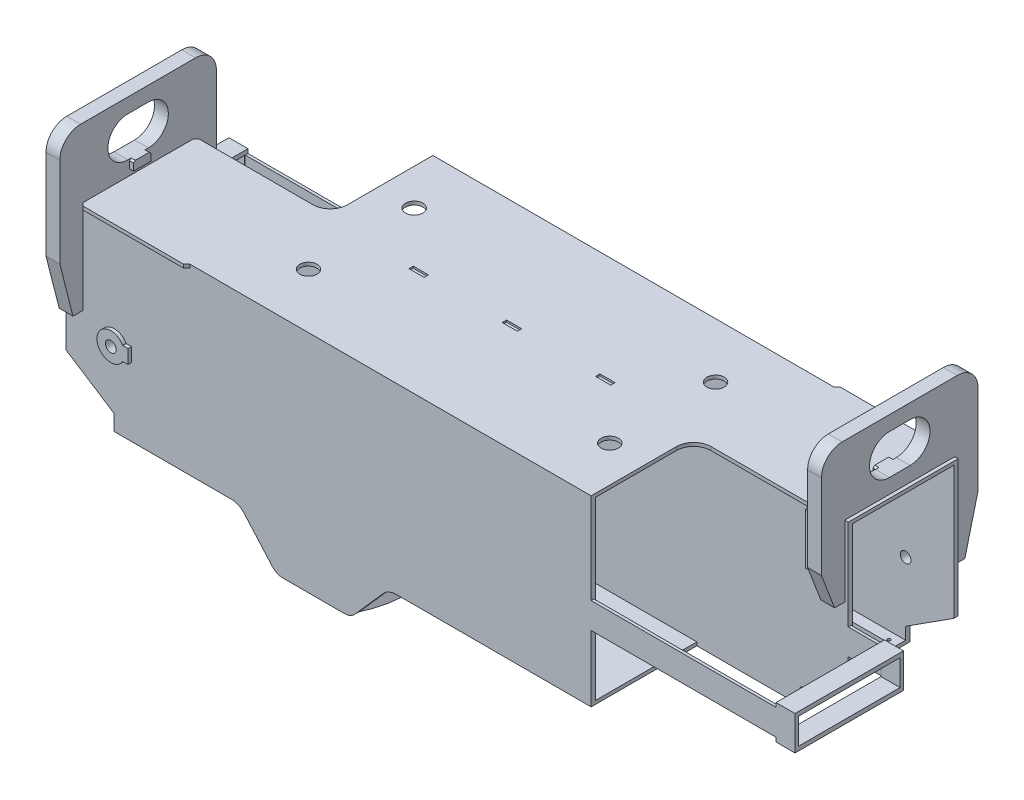
SolidWorks part; units mm, degrees
ref_plane "正面" through (0, 0, 0) normal (0, 0, 1) x (1, 0, 0)
ref_plane "平面" through (0, 0, 0) normal (0, 1, 0) x (1, 0, 0)
ref_plane "右側面" through (0, 0, 0) normal (1, 0, 0) x (0, 0, -1)
ref_plane "平面1" through (0, 0, -306) normal (0, 0, 1) x (1, 0, 0)
sketch "ｽｹｯﾁ2" plane through (0, 0, -306) normal (0, 0, 1) x (1, 0, 0)
  line L0 (140, 0) -> (478.29, 0)
  line L1 (515.7605, -16.8947) -> (597.5636, -109.4842)
  line L2 (627.54, -123) -> (806.46, -123)
  line L3 (836.4364, -109.4842) -> (918.2395, -16.8947)
  line L4 (955.71, 0) -> (1002.29, 0)
  line L5 (1039.7605, -16.8947) -> (1121.5636, -109.4842)
  line L6 (1151.54, -123) -> (1330.46, -123)
  line L7 (1360.4364, -109.4842) -> (1442.2395, -16.8947)
  line L8 (1479.71, 0) -> (1818, 0)
  line L9 (1818, 0) -> (1818, 45)
  line L10 (1818, 45) -> (1958, 135)
  line L11 (1958, 135) -> (1958, 519)
  line L12 (1958, 519) -> (0, 519)
  line L13 (0, 519) -> (0, 135)
  line L14 (0, 135) -> (140, 45)
  line L15 (140, 45) -> (140, 0)
  arc A0 (478.29, 0) -> (515.7605, -16.8947) centre (478.29, -50) cw
  arc A1 (597.5636, -109.4842) -> (627.54, -123) centre (627.54, -83) ccw
  arc A2 (806.46, -123) -> (836.4364, -109.4842) centre (806.46, -83) ccw
  arc A3 (918.2395, -16.8947) -> (955.71, 0) centre (955.71, -50) cw
  arc A4 (1002.29, 0) -> (1039.7605, -16.8947) centre (1002.29, -50) cw
  arc A5 (1121.5636, -109.4842) -> (1151.54, -123) centre (1151.54, -83) ccw
  arc A6 (1330.46, -123) -> (1360.4364, -109.4842) centre (1330.46, -83) ccw
  arc A7 (1442.2395, -16.8947) -> (1479.71, 0) centre (1479.71, -50) cw
extrude "ﾎﾞｽ - 押し出し1" add sketch "ｽｹｯﾁ2" against normal blind 12
sketch "ｽｹｯﾁ3" plane through (0, 0, 0) normal (0, 0, 1) x (1, 0, 0)
  line L0 (140, 0) -> (478.29, 0)
  line L1 (515.7605, -16.8947) -> (597.5636, -109.4842)
  line L2 (627.54, -123) -> (806.46, -123)
  line L3 (836.4364, -109.4842) -> (918.2395, -16.8947)
  line L4 (955.71, 0) -> (1520, 0)
  line L5 (1520, 0) -> (1520, 519)
  line L6 (1520, 519) -> (0, 519)
  line L7 (0, 519) -> (0, 135)
  line L8 (0, 135) -> (140, 45)
  line L9 (140, 45) -> (140, 0)
  arc A0 (478.29, 0) -> (515.7605, -16.8947) centre (478.29, -50) cw
  arc A1 (597.5636, -109.4842) -> (627.54, -123) centre (627.54, -83) ccw
  arc A2 (806.46, -123) -> (836.4364, -109.4842) centre (806.46, -83) ccw
  arc A3 (918.2395, -16.8947) -> (955.71, 0) centre (955.71, -50) cw
extrude "ﾎﾞｽ - 押し出し2" add sketch "ｽｹｯﾁ3" against normal blind 12
sketch "ｽｹｯﾁ4" plane through (0, 0, 0) normal (0, 0, 1) x (1, 0, 0)
  circle A0 centre (140, 218) radius 15.5
extrude "ｶｯﾄ - 押し出し1" cut sketch "ｽｹｯﾁ4" against normal blind 12
ref_plane "平面2" through (0, 0, -612) normal (0, 0, 1) x (1, 0, 0)
sketch "ｽｹｯﾁ6" plane through (0, 0, -612) normal (0, 0, 1) x (1, 0, 0)
  line L0 (1818, 0) -> (1479.71, 0)
  line L1 (1442.2395, -16.8947) -> (1360.4364, -109.4842)
  line L2 (1330.46, -123) -> (1151.54, -123)
  line L3 (1121.5636, -109.4842) -> (1039.7605, -16.8947)
  line L4 (1002.29, 0) -> (438, 0)
  line L5 (438, 0) -> (438, 519)
  line L6 (438, 519) -> (1958, 519)
  line L7 (1958, 519) -> (1958, 135)
  line L8 (1958, 135) -> (1818, 45)
  line L9 (1818, 45) -> (1818, 0)
  arc A0 (1479.71, 0) -> (1442.2395, -16.8947) centre (1479.71, -50) ccw
  arc A1 (1360.4364, -109.4842) -> (1330.46, -123) centre (1330.46, -83) cw
  arc A2 (1151.54, -123) -> (1121.5636, -109.4842) centre (1151.54, -83) cw
  arc A3 (1039.7605, -16.8947) -> (1002.29, 0) centre (1002.29, -50) ccw
extrude "ﾎﾞｽ - 押し出し3" add sketch "ｽｹｯﾁ6" against normal blind 12
sketch "ｽｹｯﾁ7" plane through (0, 0, -612) normal (0, 0, 1) x (1, 0, 0)
  circle A0 centre (1818, 218) radius 15.5
extrude "ｶｯﾄ - 押し出し2" cut sketch "ｽｹｯﾁ7" against normal blind 12
ref_plane "平面3" through (0, 519, 0) normal (0, 1, 0) x (1, 0, 0)
sketch "ｽｹｯﾁ9" plane through (0, 519, 0) normal (0, 1, 0) x (1, 0, 0)
  line L0 (0, 0) -> (50, 0)
  line L1 (50, 0) -> (59, -9)
  line L2 (59, -9) -> (350, -9)
  line L3 (350, -9) -> (359, 0)
  line L4 (359, 0) -> (1520, 0)
  line L5 (1520, 0) -> (1520, 247)
  line L6 (1570, 297) -> (1899, 297)
  line L7 (1899, 297) -> (1908, 306)
  line L8 (1908, 306) -> (1958, 306)
  line L9 (1958, 306) -> (1958, 624)
  line L10 (1958, 624) -> (1908, 624)
  line L11 (1908, 624) -> (1899, 633)
  line L12 (1899, 633) -> (1608, 633)
  line L13 (1608, 633) -> (1599, 624)
  line L14 (1599, 624) -> (438, 624)
  line L15 (438, 624) -> (438, 377)
  line L16 (388, 327) -> (59, 327)
  line L17 (59, 327) -> (50, 318)
  line L18 (50, 318) -> (0, 318)
  line L19 (0, 318) -> (0, 0)
  arc A0 (1520, 247) -> (1570, 297) centre (1570, 247) cw
  arc A1 (438, 377) -> (388, 327) centre (388, 377) cw
extrude "ﾎﾞｽ - 押し出し4" add sketch "ｽｹｯﾁ9" along normal blind 10
sketch "ｽｹｯﾁ10" plane through (0, 519, 0) normal (0, 1, 0) x (1, 0, 0)
  circle A0 centre (543, 159) radius 25
  circle A1 centre (1415, 159) radius 25
  circle A2 centre (543, 465) radius 25
  circle A3 centre (1415, 465) radius 25
sketch "ｽｹｯﾁ11" plane through (0, 519, 0) normal (0, 1, 0) x (1, 0, 0)
  circle A0 centre (543, 159) radius 25
  circle A1 centre (1415, 159) radius 25
  circle A2 centre (543, 465) radius 25
  circle A3 centre (1415, 465) radius 25
extrude "ｶｯﾄ - 押し出し4" cut sketch "ｽｹｯﾁ11" along normal blind 10
sketch "ｽｹｯﾁ12" plane through (0, 519, 0) normal (0, 1, 0) x (1, 0, 0)
  line L0 (687, 305.75) -> (731, 305.75)
  line L1 (731, 305.75) -> (731, 318.25)
  line L2 (731, 318.25) -> (687, 318.25)
  line L3 (687, 318.25) -> (687, 305.75)
  line L4 (957, 305.75) -> (1001, 305.75)
  line L5 (1001, 305.75) -> (1001, 318.25)
  line L6 (1001, 318.25) -> (957, 318.25)
  line L7 (957, 318.25) -> (957, 305.75)
  line L8 (1227, 305.75) -> (1271, 305.75)
  line L9 (1271, 305.75) -> (1271, 318.25)
  line L10 (1271, 318.25) -> (1227, 318.25)
  line L11 (1227, 318.25) -> (1227, 305.75)
sketch "ｽｹｯﾁ13" plane through (0, 519, 0) normal (0, 1, 0) x (1, 0, 0)
  line L0 (687, 305.75) -> (731, 305.75)
  line L1 (731, 305.75) -> (731, 318.25)
  line L2 (731, 318.25) -> (687, 318.25)
  line L3 (687, 318.25) -> (687, 305.75)
  line L4 (957, 305.75) -> (1001, 305.75)
  line L5 (1001, 305.75) -> (1001, 318.25)
  line L6 (1001, 318.25) -> (957, 318.25)
  line L7 (957, 318.25) -> (957, 305.75)
  line L8 (1227, 305.75) -> (1271, 305.75)
  line L9 (1271, 305.75) -> (1271, 318.25)
  line L10 (1271, 318.25) -> (1227, 318.25)
  line L11 (1227, 318.25) -> (1227, 305.75)
extrude "ｶｯﾄ - 押し出し6" cut sketch "ｽｹｯﾁ13" along normal blind 10
sketch "ｽｹｯﾁ14" plane through (0, 519, 0) normal (0, 1, 0) x (1, 0, 0)
  line L0 (687, 306) -> (731, 306)
  line L1 (731, 306) -> (731, 318)
  line L2 (731, 318) -> (687, 318)
  line L3 (687, 318) -> (687, 306)
  line L4 (957, 306) -> (1001, 306)
  line L5 (1001, 306) -> (1001, 318)
  line L6 (1001, 318) -> (957, 318)
  line L7 (957, 318) -> (957, 306)
  line L8 (1227, 306) -> (1271, 306)
  line L9 (1271, 306) -> (1271, 318)
  line L10 (1271, 318) -> (1227, 318)
  line L11 (1227, 318) -> (1227, 306)
extrude "ﾎﾞｽ - 押し出し5" add sketch "ｽｹｯﾁ14" along normal blind 5
sketch "ｽｹｯﾁ15" plane through (0, 0, 0) normal (0, 1, 0) x (1, 0, 0)
  line L0 (140, 12) -> (1520, 12)
  line L1 (1520, 12) -> (1520, 306)
  line L2 (1520, 306) -> (140, 306)
  line L3 (140, 306) -> (140, 204)
  line L4 (140, 204) -> (170, 204)
  line L5 (170, 114) -> (140, 114)
  line L6 (140, 114) -> (140, 12)
  arc A0 (170, 204) -> (215, 159) centre (170, 159) cw
  arc A1 (215, 159) -> (170, 114) centre (170, 159) cw
extrude "ﾎﾞｽ - 押し出し6" add sketch "ｽｹｯﾁ15" along normal blind 10
sketch "ｽｹｯﾁ16" plane through (0, 0, 0) normal (0, 1, 0) x (1, 0, 0)
  line L0 (159, 43) -> (300, 43)
  line L1 (300, 43) -> (300, 74)
  line L2 (300, 74) -> (159, 74)
  line L3 (159, 74) -> (159, 43)
  line L4 (159, 244) -> (300, 244)
  line L5 (300, 244) -> (300, 275)
  line L6 (300, 275) -> (159, 275)
  line L7 (159, 275) -> (159, 244)
  circle A0 centre (165.5, 34.5) radius 4.5
  circle A1 centre (293.5, 34.5) radius 4.5
  circle A2 centre (165.5, 82.5) radius 4.5
  circle A3 centre (293.5, 82.5) radius 4.5
  circle A4 centre (165.5, 235.5) radius 4.5
  circle A5 centre (293.5, 235.5) radius 4.5
  circle A6 centre (165.5, 283.5) radius 4.5
  circle A7 centre (293.5, 283.5) radius 4.5
sketch "ｽｹｯﾁ17" plane through (0, 0, 0) normal (0, 1, 0) x (1, 0, 0)
  line L0 (159, 43) -> (300, 43)
  line L1 (300, 43) -> (300, 74)
  line L2 (300, 74) -> (159, 74)
  line L3 (159, 74) -> (159, 43)
  line L4 (159, 244) -> (300, 244)
  line L5 (300, 244) -> (300, 275)
  line L6 (300, 275) -> (159, 275)
  line L7 (159, 275) -> (159, 244)
  circle A0 centre (165.5, 34.5) radius 4.5
  circle A1 centre (293.5, 34.5) radius 4.5
  circle A2 centre (165.5, 82.5) radius 4.5
  circle A3 centre (293.5, 82.5) radius 4.5
  circle A4 centre (165.5, 235.5) radius 4.5
  circle A5 centre (293.5, 235.5) radius 4.5
  circle A6 centre (165.5, 283.5) radius 4.5
  circle A7 centre (293.5, 283.5) radius 4.5
extrude "ｶｯﾄ - 押し出し8" cut sketch "ｽｹｯﾁ17" along normal blind 10
sketch "ｽｹｯﾁ18" plane through (0, 0, 0) normal (0, 1, 0) x (1, 0, 0)
  line L0 (1818, 612) -> (438, 612)
  line L1 (438, 612) -> (438, 318)
  line L2 (438, 318) -> (1818, 318)
  line L3 (1818, 318) -> (1818, 420)
  line L4 (1818, 420) -> (1788, 420)
  line L5 (1788, 510) -> (1818, 510)
  line L6 (1818, 510) -> (1818, 612)
  arc A0 (1788, 420) -> (1743, 465) centre (1788, 465) cw
  arc A1 (1743, 465) -> (1788, 510) centre (1788, 465) cw
extrude "ﾎﾞｽ - 押し出し7" add sketch "ｽｹｯﾁ18" along normal blind 10
sketch "ｽｹｯﾁ19" plane through (0, 0, 0) normal (0, 1, 0) x (1, 0, 0)
  line L0 (1658, 550) -> (1799, 550)
  line L1 (1799, 550) -> (1799, 581)
  line L2 (1799, 581) -> (1658, 581)
  line L3 (1658, 581) -> (1658, 550)
  line L4 (1658, 349) -> (1799, 349)
  line L5 (1799, 349) -> (1799, 380)
  line L6 (1799, 380) -> (1658, 380)
  line L7 (1658, 380) -> (1658, 349)
  circle A0 centre (1792.5, 589.5) radius 4.5
  circle A1 centre (1664.5, 589.5) radius 4.5
  circle A2 centre (1792.5, 541.5) radius 4.5
  circle A3 centre (1664.5, 541.5) radius 4.5
  circle A4 centre (1792.5, 388.5) radius 4.5
  circle A5 centre (1664.5, 388.5) radius 4.5
  circle A6 centre (1792.5, 340.5) radius 4.5
  circle A7 centre (1664.5, 340.5) radius 4.5
sketch "ｽｹｯﾁ20" plane through (0, 0, 0) normal (0, 1, 0) x (1, 0, 0)
  line L0 (1658, 550) -> (1799, 550)
  line L1 (1799, 550) -> (1799, 581)
  line L2 (1799, 581) -> (1658, 581)
  line L3 (1658, 581) -> (1658, 550)
  line L4 (1658, 349) -> (1799, 349)
  line L5 (1799, 349) -> (1799, 380)
  line L6 (1799, 380) -> (1658, 380)
  line L7 (1658, 380) -> (1658, 349)
  circle A0 centre (1792.5, 589.5) radius 4.5
  circle A1 centre (1664.5, 589.5) radius 4.5
  circle A2 centre (1792.5, 541.5) radius 4.5
  circle A3 centre (1664.5, 541.5) radius 4.5
  circle A4 centre (1792.5, 388.5) radius 4.5
  circle A5 centre (1664.5, 388.5) radius 4.5
  circle A6 centre (1792.5, 340.5) radius 4.5
  circle A7 centre (1664.5, 340.5) radius 4.5
extrude "ｶｯﾄ - 押し出し10" cut sketch "ｽｹｯﾁ20" along normal blind 10
ref_plane "平面4" through (10, 0, 0) normal (1, 0, 0) x (0, 0, -1)
sketch "ｽｹｯﾁ22" plane through (10, 0, 0) normal (1, 0, 0) x (0, 0, -1)
  line L0 (0, 259) -> (-29.5, 259)
  line L1 (-29.5, 259) -> (-67.5, 409)
  line L2 (-67.5, 409) -> (-67.5, 669)
  line L3 (-7.5, 729) -> (325.5, 729)
  line L4 (385.5, 669) -> (385.5, 424)
  line L5 (385.5, 424) -> (347.5, 324)
  line L6 (347.5, 324) -> (318, 324)
  line L7 (318, 324) -> (318, 529)
  line L8 (318, 529) -> (0, 529)
  line L9 (0, 529) -> (0, 259)
  arc A0 (-67.5, 669) -> (-7.5, 729) centre (-7.5, 669) cw
  arc A1 (325.5, 729) -> (385.5, 669) centre (325.5, 669) cw
extrude "ﾎﾞｽ - 押し出し8" add sketch "ｽｹｯﾁ22" along normal blind 40
sketch "ｽｹｯﾁ23" plane through (10, 0, 0) normal (1, 0, 0) x (0, 0, -1)
  line L0 (129, 686.5) -> (189, 686.5)
  line L1 (189, 571.5) -> (129, 571.5)
  arc A0 (189, 686.5) -> (246.5, 629) centre (189, 629) cw
  arc A1 (246.5, 629) -> (189, 571.5) centre (189, 629) cw
  arc A2 (129, 571.5) -> (71.5, 629) centre (129, 629) cw
  arc A3 (71.5, 629) -> (129, 686.5) centre (129, 629) cw
sketch "ｽｹｯﾁ24" plane through (10, 0, 0) normal (1, 0, 0) x (0, 0, -1)
  line L0 (129, 686.5) -> (189, 686.5)
  line L1 (189, 571.5) -> (129, 571.5)
  arc A0 (189, 686.5) -> (246.5, 629) centre (189, 629) cw
  arc A1 (246.5, 629) -> (189, 571.5) centre (189, 629) cw
  arc A2 (129, 571.5) -> (71.5, 629) centre (129, 629) cw
  arc A3 (71.5, 629) -> (129, 686.5) centre (129, 629) cw
extrude "ｶｯﾄ - 押し出し12" cut sketch "ｽｹｯﾁ24" along normal blind 40
ref_plane "平面5" through (1908, 0, 0) normal (1, 0, 0) x (0, 0, -1)
sketch "ｽｹｯﾁ26" plane through (1908, 0, 0) normal (1, 0, 0) x (0, 0, -1)
  line L0 (624, 259) -> (653.5, 259)
  line L1 (653.5, 259) -> (691.5, 409)
  line L2 (691.5, 409) -> (691.5, 669)
  line L3 (631.5, 729) -> (298.5, 729)
  line L4 (238.5, 669) -> (238.5, 424)
  line L5 (238.5, 424) -> (276.5, 324)
  line L6 (276.5, 324) -> (306, 324)
  line L7 (306, 324) -> (306, 529)
  line L8 (306, 529) -> (624, 529)
  line L9 (624, 529) -> (624, 259)
  arc A0 (691.5, 669) -> (631.5, 729) centre (631.5, 669) ccw
  arc A1 (298.5, 729) -> (238.5, 669) centre (298.5, 669) ccw
extrude "ﾎﾞｽ - 押し出し9" add sketch "ｽｹｯﾁ26" along normal blind 40
sketch "ｽｹｯﾁ27" plane through (1908, 0, 0) normal (1, 0, 0) x (0, 0, -1)
  line L0 (495, 686.5) -> (435, 686.5)
  line L1 (435, 571.5) -> (495, 571.5)
  arc A0 (435, 686.5) -> (377.5, 629) centre (435, 629) ccw
  arc A1 (377.5, 629) -> (435, 571.5) centre (435, 629) ccw
  arc A2 (495, 571.5) -> (552.5, 629) centre (495, 629) ccw
  arc A3 (552.5, 629) -> (495, 686.5) centre (495, 629) ccw
sketch "ｽｹｯﾁ28" plane through (1908, 0, 0) normal (1, 0, 0) x (0, 0, -1)
  line L0 (495, 686.5) -> (435, 686.5)
  line L1 (435, 571.5) -> (495, 571.5)
  arc A0 (435, 686.5) -> (377.5, 629) centre (435, 629) ccw
  arc A1 (377.5, 629) -> (435, 571.5) centre (435, 629) ccw
  arc A2 (495, 571.5) -> (552.5, 629) centre (495, 629) ccw
  arc A3 (552.5, 629) -> (495, 686.5) centre (495, 629) ccw
extrude "ｶｯﾄ - 押し出し14" cut sketch "ｽｹｯﾁ28" along normal blind 40
sketch "ｽｹｯﾁ29" plane through (0, 0, 0) normal (0, 1, 0) x (1, 0, 0)
  line L0 (657, 27) -> (777, 27)
  line L1 (777, 27) -> (782, 32)
  line L2 (782, 32) -> (782, 286)
  line L3 (782, 286) -> (777, 291)
  line L4 (777, 291) -> (657, 291)
  line L5 (657, 291) -> (652, 286)
  line L6 (652, 286) -> (652, 32)
  line L7 (652, 32) -> (657, 27)
extrude "ﾎﾞｽ - 押し出し10" add sketch "ｽｹｯﾁ29" against normal blind 12
ref_plane "平面6" through (712, 0, 0) normal (1, 0, 0) x (0, 0, -1)
sketch "ｽｹｯﾁ31" plane through (712, 0, 0) normal (1, 0, 0) x (0, 0, -1)
  line L0 (12, -15) -> (306, -15)
  line L1 (306, -15) -> (306, -145)
  line L2 (306, -145) -> (12, -145)
  line L3 (12, -145) -> (12, -15)
extrude "ﾎﾞｽ - 押し出し11" add sketch "ｽｹｯﾁ31" along normal blind 10
ref_plane "平面7" through (0, 0, -12) normal (0, 0, 1) x (1, 0, 0)
sketch "ｽｹｯﾁ33" plane through (0, 0, -12) normal (0, 0, 1) x (1, 0, 0)
  line L0 (761, -15) -> (772.547, -15)
  line L1 (772.547, -15) -> (847.6025, -145)
  line L2 (847.6025, -145) -> (836.0555, -145)
  line L3 (836.0555, -145) -> (761, -15)
  line L4 (673, -15) -> (661.453, -15)
  line L5 (661.453, -15) -> (586.3975, -145)
  line L6 (586.3975, -145) -> (597.9445, -145)
  line L7 (597.9445, -145) -> (673, -15)
extrude "ﾎﾞｽ - 押し出し12" add sketch "ｽｹｯﾁ33" against normal blind 294
sketch "ｽｹｯﾁ34" plane through (0, 0, 0) normal (1, 0, 0) x (0, 0, -1)
  line L0 (306, -114.1033) -> (306, -260)
  line L1 (306, -260) -> (12, -260)
  line L2 (12, -260) -> (12, -114.1033)
  arc A0 (12, -114.1033) -> (306, -114.1033) centre (159, 483.07) ccw
extrude "ｶｯﾄ - 押し出し15" cut sketch "ｽｹｯﾁ34" against normal through all and the other way through all
sketch "ｽｹｯﾁ35" plane through (0, 0, 0) normal (1, 0, 0) x (0, 0, -1)
  line L0 (119, -40) -> (199, -40)
  line L1 (199, -100) -> (119, -100)
  arc A0 (199, -40) -> (229, -70) centre (199, -70) cw
  arc A1 (229, -70) -> (199, -100) centre (199, -70) cw
  arc A2 (119, -100) -> (89, -70) centre (119, -70) cw
  arc A3 (89, -70) -> (119, -40) centre (119, -70) cw
extrude "ｶｯﾄ - 押し出し16" cut sketch "ｽｹｯﾁ35" against normal through all and the other way through all
sketch "ｽｹｯﾁ36" plane through (0, 0, 0) normal (0, 1, 0) x (1, 0, 0)
  line L0 (1181, 333) -> (1301, 333)
  line L1 (1301, 333) -> (1306, 338)
  line L2 (1306, 338) -> (1306, 592)
  line L3 (1306, 592) -> (1301, 597)
  line L4 (1301, 597) -> (1181, 597)
  line L5 (1181, 597) -> (1176, 592)
  line L6 (1176, 592) -> (1176, 338)
  line L7 (1176, 338) -> (1181, 333)
extrude "ﾎﾞｽ - 押し出し13" add sketch "ｽｹｯﾁ36" against normal blind 12
ref_plane "平面8" through (1236, 0, 0) normal (1, 0, 0) x (0, 0, -1)
sketch "ｽｹｯﾁ38" plane through (1236, 0, 0) normal (1, 0, 0) x (0, 0, -1)
  line L0 (318, -15) -> (612, -15)
  line L1 (612, -15) -> (612, -145)
  line L2 (612, -145) -> (318, -145)
  line L3 (318, -145) -> (318, -15)
extrude "ﾎﾞｽ - 押し出し14" add sketch "ｽｹｯﾁ38" along normal blind 10
ref_plane "平面9" through (0, 0, -318) normal (0, 0, 1) x (1, 0, 0)
sketch "ｽｹｯﾁ40" plane through (0, 0, -318) normal (0, 0, 1) x (1, 0, 0)
  line L0 (1285, -15) -> (1296.547, -15)
  line L1 (1296.547, -15) -> (1371.6025, -145)
  line L2 (1371.6025, -145) -> (1360.0555, -145)
  line L3 (1360.0555, -145) -> (1285, -15)
  line L4 (1197, -15) -> (1185.453, -15)
  line L5 (1185.453, -15) -> (1110.3975, -145)
  line L6 (1110.3975, -145) -> (1121.9445, -145)
  line L7 (1121.9445, -145) -> (1197, -15)
extrude "ﾎﾞｽ - 押し出し15" add sketch "ｽｹｯﾁ40" against normal blind 294
sketch "ｽｹｯﾁ41" plane through (0, 0, 0) normal (1, 0, 0) x (0, 0, -1)
  line L0 (612, -114.1033) -> (612, -260)
  line L1 (612, -260) -> (318, -260)
  line L2 (318, -260) -> (318, -114.1033)
  arc A0 (318, -114.1033) -> (612, -114.1033) centre (465, 483.07) ccw
extrude "ｶｯﾄ - 押し出し17" cut sketch "ｽｹｯﾁ41" against normal through all and the other way through all
sketch "ｽｹｯﾁ42" plane through (0, 0, 0) normal (1, 0, 0) x (0, 0, -1)
  line L0 (425, -40) -> (505, -40)
  line L1 (505, -100) -> (425, -100)
  arc A0 (505, -40) -> (535, -70) centre (505, -70) cw
  arc A1 (535, -70) -> (505, -100) centre (505, -70) cw
  arc A2 (425, -100) -> (395, -70) centre (425, -70) cw
  arc A3 (395, -70) -> (425, -40) centre (425, -70) cw
extrude "ｶｯﾄ - 押し出し18" cut sketch "ｽｹｯﾁ42" against normal through all and the other way through all
ref_plane "平面10" through (0, 0, -616) normal (0, 0, 1) x (1, 0, 0)
sketch "ｽｹｯﾁ44" plane through (0, 0, -616) normal (0, 0, 1) x (1, 0, 0)
  line L0 (-97, 191.5) -> (438, 191.5)
  line L1 (438, 191.5) -> (438, 266.5)
  line L2 (438, 266.5) -> (-97, 266.5)
  line L3 (-97, 266.5) -> (-97, 191.5)
extrude "ﾎﾞｽ - 押し出し16" add sketch "ｽｹｯﾁ44" against normal blind 8
sketch "ｽｹｯﾁ45" plane through (0, 0, 0) normal (0, 0, 1) x (1, 0, 0)
  line L0 (1520, 191.5) -> (2055, 191.5)
  line L1 (2055, 191.5) -> (2055, 266.5)
  line L2 (2055, 266.5) -> (1520, 266.5)
  line L3 (1520, 266.5) -> (1520, 191.5)
extrude "ﾎﾞｽ - 押し出し17" add sketch "ｽｹｯﾁ45" against normal blind 8
ref_plane "平面11" through (0, 0, -310) normal (0, 0, 1) x (1, 0, 0)
sketch "ｽｹｯﾁ47" plane through (0, 0, -310) normal (0, 0, 1) x (1, 0, 0)
  line L0 (-97, 191.5) -> (0, 191.5)
  line L1 (0, 191.5) -> (0, 266.5)
  line L2 (0, 266.5) -> (-97, 266.5)
  line L3 (-97, 266.5) -> (-97, 191.5)
extrude "ﾎﾞｽ - 押し出し18" add sketch "ｽｹｯﾁ47" against normal blind 8
sketch "ｽｹｯﾁ48" plane through (0, 0, -306) normal (0, 0, 1) x (1, 0, 0)
  line L0 (1958, 191.5) -> (2055, 191.5)
  line L1 (2055, 191.5) -> (2055, 266.5)
  line L2 (2055, 266.5) -> (1958, 266.5)
  line L3 (1958, 266.5) -> (1958, 191.5)
extrude "ﾎﾞｽ - 押し出し19" add sketch "ｽｹｯﾁ48" against normal blind 8
ref_plane "平面12" through (-152, 0, 0) normal (1, 0, 0) x (0, 0, -1)
sketch "ｽｹｯﾁ50" plane through (-152, 0, 0) normal (1, 0, 0) x (0, 0, -1)
  line L0 (310, 179.5) -> (624, 179.5)
  line L1 (624, 179.5) -> (624, 278.5)
  line L2 (624, 278.5) -> (310, 278.5)
  line L3 (310, 278.5) -> (310, 179.5)
extrude "ﾎﾞｽ - 押し出し20" add sketch "ｽｹｯﾁ50" along normal blind 55
sketch "ｽｹｯﾁ51" plane through (-152, 0, 0) normal (1, 0, 0) x (0, 0, -1)
  line L0 (320, 191.5) -> (614, 191.5)
  line L1 (614, 191.5) -> (614, 266.5)
  line L2 (614, 266.5) -> (320, 266.5)
  line L3 (320, 266.5) -> (320, 191.5)
sketch "ｽｹｯﾁ52" plane through (-152, 0, 0) normal (1, 0, 0) x (0, 0, -1)
  line L0 (320, 191.5) -> (614, 191.5)
  line L1 (614, 191.5) -> (614, 266.5)
  line L2 (614, 266.5) -> (320, 266.5)
  line L3 (320, 266.5) -> (320, 191.5)
extrude "ｶｯﾄ - 押し出し20" cut sketch "ｽｹｯﾁ52" along normal blind 55
ref_plane "平面13" through (2055, 0, 0) normal (1, 0, 0) x (0, 0, -1)
sketch "ｽｹｯﾁ54" plane through (2055, 0, 0) normal (1, 0, 0) x (0, 0, -1)
  line L0 (0, 179.5) -> (314, 179.5)
  line L1 (314, 179.5) -> (314, 278.5)
  line L2 (314, 278.5) -> (0, 278.5)
  line L3 (0, 278.5) -> (0, 179.5)
extrude "ﾎﾞｽ - 押し出し21" add sketch "ｽｹｯﾁ54" along normal blind 55
sketch "ｽｹｯﾁ55" plane through (2055, 0, 0) normal (1, 0, 0) x (0, 0, -1)
  line L0 (10, 191.5) -> (304, 191.5)
  line L1 (304, 191.5) -> (304, 266.5)
  line L2 (304, 266.5) -> (10, 266.5)
  line L3 (10, 266.5) -> (10, 191.5)
sketch "ｽｹｯﾁ56" plane through (2055, 0, 0) normal (1, 0, 0) x (0, 0, -1)
  line L0 (10, 191.5) -> (304, 191.5)
  line L1 (304, 191.5) -> (304, 266.5)
  line L2 (304, 266.5) -> (10, 266.5)
  line L3 (10, 266.5) -> (10, 191.5)
extrude "ｶｯﾄ - 押し出し22" cut sketch "ｽｹｯﾁ56" along normal blind 55
sketch "ｽｹｯﾁ57" plane through (0, 0, 0) normal (0, 1, 0) x (1, 0, 0)
  line L0 (152, 26) -> (307, 26)
  line L1 (312, 31) -> (312, 86)
  line L2 (307, 91) -> (152, 91)
  line L3 (147, 86) -> (147, 31)
  line L4 (152, 227) -> (307, 227)
  line L5 (312, 232) -> (312, 287)
  line L6 (307, 292) -> (152, 292)
  line L7 (147, 287) -> (147, 232)
  arc A0 (307, 26) -> (312, 31) centre (307, 31) ccw
  arc A1 (312, 86) -> (307, 91) centre (307, 86) ccw
  arc A2 (152, 91) -> (147, 86) centre (152, 86) ccw
  arc A3 (147, 31) -> (152, 26) centre (152, 31) ccw
  arc A4 (307, 227) -> (312, 232) centre (307, 232) ccw
  arc A5 (312, 287) -> (307, 292) centre (307, 287) ccw
  arc A6 (152, 292) -> (147, 287) centre (152, 287) ccw
  arc A7 (147, 232) -> (152, 227) centre (152, 232) ccw
extrude "ﾎﾞｽ - 押し出し22" add sketch "ｽｹｯﾁ57" against normal blind 12
sketch "ｽｹｯﾁ58" plane through (0, 0, 0) normal (0, 1, 0) x (1, 0, 0)
  line L0 (174.5, 74) -> (284.5, 74)
  line L1 (284.5, 43) -> (174.5, 43)
  line L2 (174.5, 275) -> (284.5, 275)
  line L3 (284.5, 244) -> (174.5, 244)
  arc A0 (284.5, 74) -> (300, 58.5) centre (284.5, 58.5) cw
  arc A1 (300, 58.5) -> (284.5, 43) centre (284.5, 58.5) cw
  arc A2 (174.5, 43) -> (159, 58.5) centre (174.5, 58.5) cw
  arc A3 (159, 58.5) -> (174.5, 74) centre (174.5, 58.5) cw
  arc A4 (284.5, 275) -> (300, 259.5) centre (284.5, 259.5) cw
  arc A5 (300, 259.5) -> (284.5, 244) centre (284.5, 259.5) cw
  arc A6 (174.5, 244) -> (159, 259.5) centre (174.5, 259.5) cw
  arc A7 (159, 259.5) -> (174.5, 275) centre (174.5, 259.5) cw
  circle A8 centre (165.5, 34.5) radius 3.4
  circle A9 centre (165.5, 82.5) radius 3.4
  circle A10 centre (293.5, 34.5) radius 3.4
  circle A11 centre (293.5, 82.5) radius 3.4
  circle A12 centre (165.5, 235.5) radius 3.4
  circle A13 centre (165.5, 283.5) radius 3.4
  circle A14 centre (293.5, 235.5) radius 3.4
  circle A15 centre (293.5, 283.5) radius 3.4
extrude "ｶｯﾄ - 押し出し23" cut sketch "ｽｹｯﾁ58" against normal blind 12
sketch "ｽｹｯﾁ59" plane through (0, 0, 0) normal (0, 1, 0) x (1, 0, 0)
  line L0 (1651, 533) -> (1806, 533)
  line L1 (1811, 538) -> (1811, 593)
  line L2 (1806, 598) -> (1651, 598)
  line L3 (1646, 593) -> (1646, 538)
  line L4 (1651, 332) -> (1806, 332)
  line L5 (1811, 337) -> (1811, 392)
  line L6 (1806, 397) -> (1651, 397)
  line L7 (1646, 392) -> (1646, 337)
  arc A0 (1806, 533) -> (1811, 538) centre (1806, 538) ccw
  arc A1 (1811, 593) -> (1806, 598) centre (1806, 593) ccw
  arc A2 (1651, 598) -> (1646, 593) centre (1651, 593) ccw
  arc A3 (1646, 538) -> (1651, 533) centre (1651, 538) ccw
  arc A4 (1806, 332) -> (1811, 337) centre (1806, 337) ccw
  arc A5 (1811, 392) -> (1806, 397) centre (1806, 392) ccw
  arc A6 (1651, 397) -> (1646, 392) centre (1651, 392) ccw
  arc A7 (1646, 337) -> (1651, 332) centre (1651, 337) ccw
extrude "ﾎﾞｽ - 押し出し23" add sketch "ｽｹｯﾁ59" against normal blind 12
sketch "ｽｹｯﾁ60" plane through (0, 0, 0) normal (0, 1, 0) x (1, 0, 0)
  line L0 (1673.5, 581) -> (1783.5, 581)
  line L1 (1783.5, 550) -> (1673.5, 550)
  line L2 (1673.5, 380) -> (1783.5, 380)
  line L3 (1783.5, 349) -> (1673.5, 349)
  arc A0 (1783.5, 581) -> (1799, 565.5) centre (1783.5, 565.5) cw
  arc A1 (1799, 565.5) -> (1783.5, 550) centre (1783.5, 565.5) cw
  arc A2 (1673.5, 550) -> (1658, 565.5) centre (1673.5, 565.5) cw
  arc A3 (1658, 565.5) -> (1673.5, 581) centre (1673.5, 565.5) cw
  arc A4 (1783.5, 380) -> (1799, 364.5) centre (1783.5, 364.5) cw
  arc A5 (1799, 364.5) -> (1783.5, 349) centre (1783.5, 364.5) cw
  arc A6 (1673.5, 349) -> (1658, 364.5) centre (1673.5, 364.5) cw
  arc A7 (1658, 364.5) -> (1673.5, 380) centre (1673.5, 364.5) cw
  circle A8 centre (1664.5, 541.5) radius 3.4
  circle A9 centre (1664.5, 589.5) radius 3.4
  circle A10 centre (1792.5, 541.5) radius 3.4
  circle A11 centre (1792.5, 589.5) radius 3.4
  circle A12 centre (1664.5, 340.5) radius 3.4
  circle A13 centre (1664.5, 388.5) radius 3.4
  circle A14 centre (1792.5, 340.5) radius 3.4
  circle A15 centre (1792.5, 388.5) radius 3.4
extrude "ｶｯﾄ - 押し出し24" cut sketch "ｽｹｯﾁ60" against normal blind 12
ref_plane "平面14" through (0, 511, 0) normal (0, 1, 0) x (1, 0, 0)
sketch "ｽｹｯﾁ62" plane through (0, 511, 0) normal (0, 1, 0) x (1, 0, 0)
  line L0 (10, 12) -> (208, 12)
  line L1 (208, 12) -> (208, 38.6)
  line L2 (208, 38.6) -> (138, 57.38)
  line L3 (138, 57.38) -> (10, 57.38)
  line L4 (10, 57.38) -> (10, 12)
  line L5 (10, 260.62) -> (208, 260.62)
  line L6 (208, 260.62) -> (208, 287.22)
  line L7 (208, 287.22) -> (138, 306)
  line L8 (138, 306) -> (10, 306)
  line L9 (10, 306) -> (10, 260.62)
extrude "ﾎﾞｽ - 押し出し24" add sketch "ｽｹｯﾁ62" along normal blind 8
sketch "ｽｹｯﾁ63" plane through (0, 511, 0) normal (0, 1, 0) x (1, 0, 0)
  line L0 (1948, 318) -> (1750, 318)
  line L1 (1750, 318) -> (1750, 344.6)
  line L2 (1750, 344.6) -> (1820, 363.38)
  line L3 (1820, 363.38) -> (1948, 363.38)
  line L4 (1948, 363.38) -> (1948, 318)
  line L5 (1948, 566.62) -> (1750, 566.62)
  line L6 (1750, 566.62) -> (1750, 593.22)
  line L7 (1750, 593.22) -> (1820, 612)
  line L8 (1820, 612) -> (1948, 612)
  line L9 (1948, 612) -> (1948, 566.62)
extrude "ﾎﾞｽ - 押し出し25" add sketch "ｽｹｯﾁ63" along normal blind 8
ref_plane "平面15" through (50, 0, 0) normal (1, 0, 0) x (0, 0, -1)
sketch "ｽｹｯﾁ65" plane through (50, 0, 0) normal (1, 0, 0) x (0, 0, -1)
  line L0 (134, 546.5) -> (184, 546.5)
  line L1 (184, 546.5) -> (184, 566.5)
  line L2 (184, 566.5) -> (179, 571.5)
  line L3 (179, 571.5) -> (139, 571.5)
  line L4 (139, 571.5) -> (134, 566.5)
  line L5 (134, 566.5) -> (134, 546.5)
extrude "ﾎﾞｽ - 押し出し26" add sketch "ｽｹｯﾁ65" along normal blind 12
ref_plane "平面16" through (1896, 0, 0) normal (1, 0, 0) x (0, 0, -1)
sketch "ｽｹｯﾁ67" plane through (1896, 0, 0) normal (1, 0, 0) x (0, 0, -1)
  line L0 (440, 546.5) -> (490, 546.5)
  line L1 (490, 546.5) -> (490, 566.5)
  line L2 (490, 566.5) -> (485, 571.5)
  line L3 (485, 571.5) -> (445, 571.5)
  line L4 (445, 571.5) -> (440, 566.5)
  line L5 (440, 566.5) -> (440, 546.5)
extrude "ﾎﾞｽ - 押し出し27" add sketch "ｽｹｯﾁ67" along normal blind 12
ref_plane "平面17" through (0, 0, -299) normal (0, 0, 1) x (1, 0, 0)
sketch "ｽｹｯﾁ69" plane through (0, 0, -299) normal (0, 0, 1) x (1, 0, 0)
  line L0 (1841, 359) -> (1896, 359)
  line L1 (1896, 359) -> (1896, 497.8333)
  line L2 (1896, 497.8333) -> (1841, 507)
  line L3 (1841, 507) -> (1841, 359)
extrude "ﾎﾞｽ - 押し出し28" add sketch "ｽｹｯﾁ69" against normal blind 7
sketch "ｽｹｯﾁ70" plane through (0, 0, -318) normal (0, 0, 1) x (1, 0, 0)
  line L0 (62, 359) -> (117, 359)
  line L1 (117, 359) -> (117, 507)
  line L2 (117, 507) -> (62, 497.8333)
  line L3 (62, 497.8333) -> (62, 359)
extrude "ﾎﾞｽ - 押し出し29" add sketch "ｽｹｯﾁ70" against normal blind 7
ref_plane "平面18" through (0, 0, 10) normal (0, 0, 1) x (1, 0, 0)
sketch "ｽｹｯﾁ72" plane through (0, 0, 10) normal (0, 0, 1) x (1, 0, 0)
  line L0 (174.641, 238) -> (190, 238)
  line L1 (190, 238) -> (190, 198)
  line L2 (190, 198) -> (174.641, 198)
  arc A0 (174.641, 198) -> (105.359, 198) centre (140, 218) cw
  arc A1 (105.359, 198) -> (140, 258) centre (140, 218) cw
  arc A2 (140, 258) -> (174.641, 238) centre (140, 218) cw
extrude "ﾎﾞｽ - 押し出し30" add sketch "ｽｹｯﾁ72" against normal blind 10
sketch "ｽｹｯﾁ73" plane through (0, 0, 10) normal (0, 0, 1) x (1, 0, 0)
  circle A0 centre (140, 218) radius 15.5
extrude "ｶｯﾄ - 押し出し25" cut sketch "ｽｹｯﾁ73" against normal blind 10
ref_plane "平面19" through (0, 0, -624) normal (0, 0, 1) x (1, 0, 0)
sketch "ｽｹｯﾁ75" plane through (0, 0, -624) normal (0, 0, 1) x (1, 0, 0)
  line L0 (1783.359, 238) -> (1768, 238)
  line L1 (1768, 238) -> (1768, 198)
  line L2 (1768, 198) -> (1783.359, 198)
  arc A0 (1783.359, 198) -> (1852.641, 198) centre (1818, 218) ccw
  arc A1 (1852.641, 198) -> (1818, 258) centre (1818, 218) ccw
  arc A2 (1818, 258) -> (1783.359, 238) centre (1818, 218) ccw
extrude "ﾎﾞｽ - 押し出し31" add sketch "ｽｹｯﾁ75" against normal blind 10
sketch "ｽｹｯﾁ76" plane through (0, 0, -624) normal (0, 0, 1) x (1, 0, 0)
  circle A0 centre (1818, 218) radius 15.5
extrude "ｶｯﾄ - 押し出し26" cut sketch "ｽｹｯﾁ76" against normal blind 10
